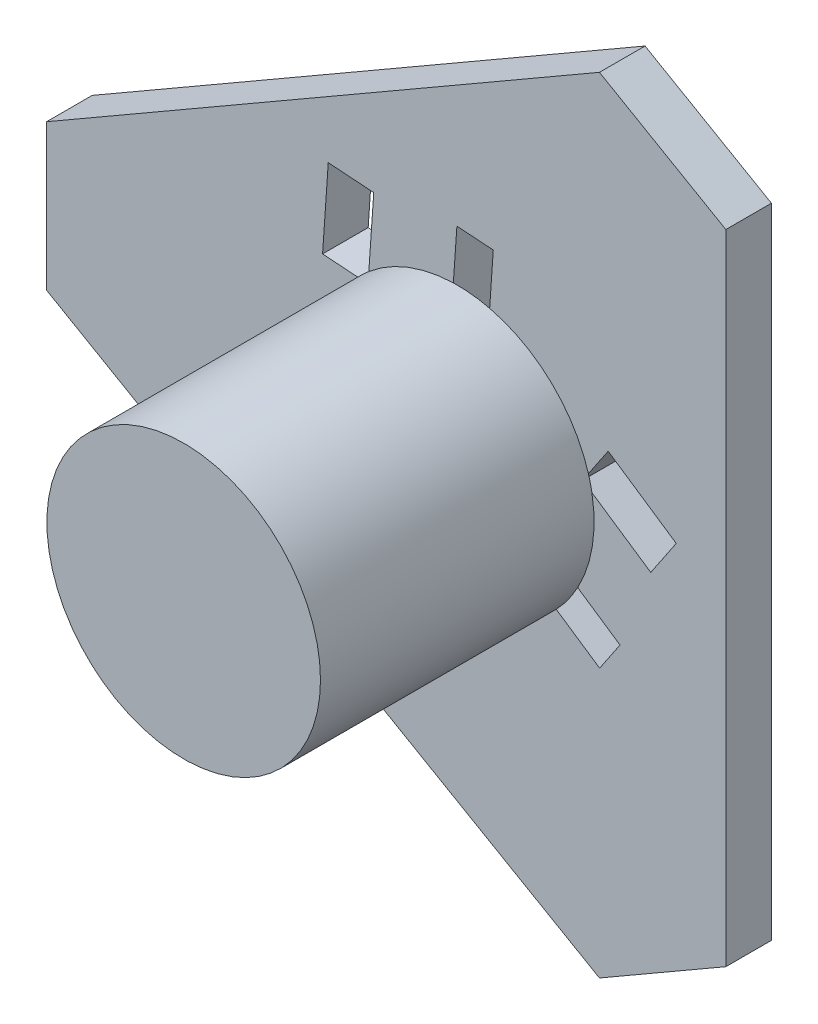
SolidWorks part; units mm, degrees
ref_plane "Plano frontal" through (0, 0, 0) normal (0, 0, 1) x (1, 0, 0)
ref_plane "Plano superior" through (0, 0, 0) normal (0, 1, 0) x (1, 0, 0)
ref_plane "Plano direito" through (0, 0, 0) normal (1, 0, 0) x (0, 0, -1)
sketch "Sketch1" plane through (0, 0, 0) normal (0, 0, 1) x (1, 0, 0)
  line L0 (-45.0333, -8) -> (-45.0333, 8)
  line L1 (-45.0333, 8) -> (15.5885, 43)
  line L2 (15.5885, 43) -> (29.4449, 35)
  line L3 (29.4449, 35) -> (29.4449, -35)
  line L4 (29.4449, -35) -> (15.5885, -43)
  line L5 (15.5885, -43) -> (-45.0333, -8)
  dimension "D1" = 60
  dimension "D2" = 60
  dimension "D3" = 60
  dimension "D4" = 16
  dimension "D5" = 16
  dimension "D6" = 16
  dimension "D7" = 120
  dimension "D8" = 120
  dimension "D9" = 120
  dimension "D10" = 120
  dimension "D11" = 120
  dimension "D12" = 120
  dimension "D13" = 70
  dimension "D14" = 70
  dimension "D15" = 70
extrude "Boss-Extrude1" add sketch "Sketch1" along normal blind 5
sketch "Sketch9" plane through (0, 0, 5) normal (0, 0, 1) x (1, 0, 0)
  line L0 (-19.5567, -6.733) -> (-7.8753, -1.0281)
  line L1 (-21.7508, -2.2402) -> (-11.2188, -23.8058) construction
  line L2 (0.4626, -18.1009) -> (-10.0695, 3.4647) construction
  line L3 (-7.8753, -1.0281) -> (-6.1199, -4.6224)
  line L4 (-6.1199, -4.6224) -> (-17.8013, -10.3273)
  line L5 (-17.8013, -10.3273) -> (-19.5567, -6.733)
  line L6 (-12.0547, -17.5367) -> (-3.9676, -13.5872)
  line L7 (-11.2188, -23.8058) -> (0.4626, -18.1009) construction
  line L8 (-3.9676, -13.5872) -> (-1.7734, -18.08)
  line L9 (-1.7734, -18.08) -> (-9.8605, -22.0295)
  line L10 (-9.8605, -22.0295) -> (-12.0547, -17.5367)
  point P12 (-2.8705, -15.8336)
  dimension "D1" = 15
  dimension "D2" = 4
  dimension "D3" = 9
  dimension "D4" = 5
  dimension "D5" = 9
  dimension "D6" = 13
  dimension "D7" = 2
extrude "Cut-Extrude7" cut sketch "Sketch9" against normal through all
sketch "Sketch10" plane through (0, 0, 0) normal (0, 1, 0) x (1, 0, 0)
  line L0 (0, 0) -> (0, -36.7235) construction
ref_axis "Axis1" through (0, 0, 0) along (0, 0, 1)
pattern_circular "CirPattern1" count 3 over 360 about axis through (0, 0, 0) along (0, 0, 1) of "Cut-Extrude7"
sketch "Sketch11" plane through (0, 0, 5) normal (0, 0, 1) x (1, 0, 0)
  circle A0 centre (0, 0) radius 15
  dimension "D1" = 30
extrude "Boss-Extrude2" add sketch "Sketch11" along normal blind 30
